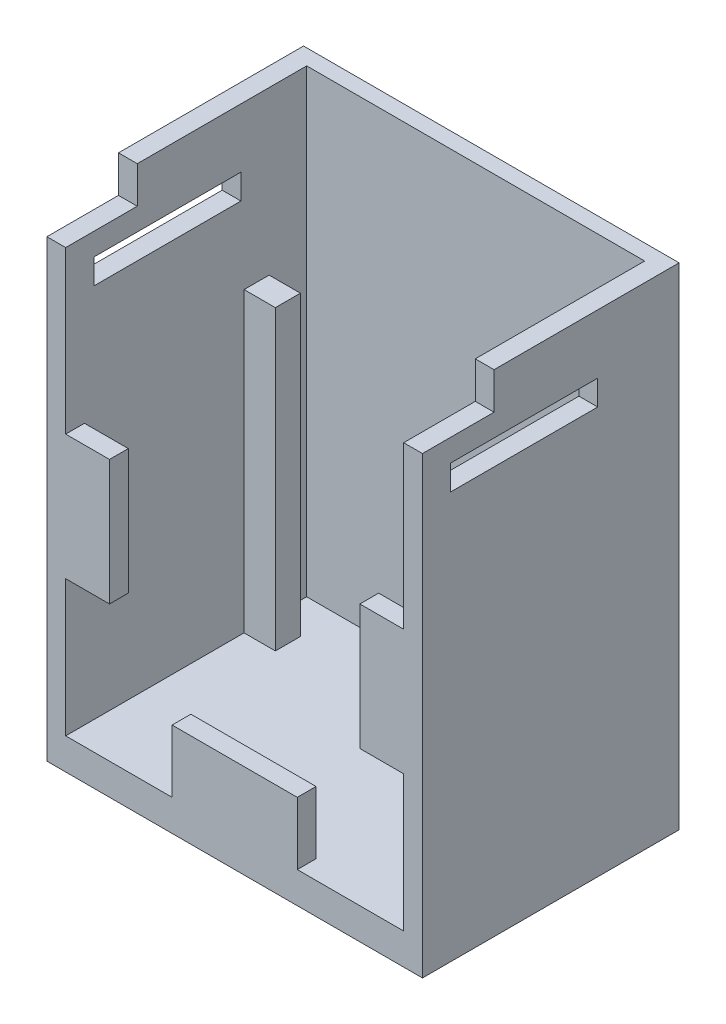
SolidWorks part; units mm, degrees
material "ABS"
ref_plane "Front Plane" through (0, 0, 0) normal (0, 0, 1) x (1, 0, 0)
ref_plane "Top Plane" through (0, 0, 0) normal (0, 1, 0) x (1, 0, 0)
ref_plane "Right Plane" through (0, 0, 0) normal (1, 0, 0) x (0, 0, -1)
sketch "Sketch1" plane through (0, 0, 0) normal (0, 0, 1) x (1, 0, 0)
  line L1 (15.24, -25.4) -> (-15.24, -25.4)
  line L2 (15.24, -25.4) -> (15.24, 15.24)
  line L3 (15.24, 15.24) -> (-15.24, 15.24)
  line L4 (-15.24, -25.4) -> (-15.24, 15.24)
  point P0 (0, 0)
  dimension "D1" = 30.48
  dimension "D2" = 40.64
extrude "Initial Block" add sketch "Sketch1" along normal blind 19.05 and the other way blind 1.778
sketch "Sketch2" plane through (0, 15.24, 0) normal (0, 1, 0) x (1, 0, 0)
  line L0 (15.24, 1.778) -> (-15.24, 1.778) construction
  line L1 (-13.716, 0.508) -> (13.716, 0.508)
  line L2 (-13.716, 0.508) -> (-13.716, -19.05)
  line L3 (-13.716, -19.05) -> (13.716, -19.05)
  line L4 (13.716, 0.508) -> (13.716, -19.05)
  line L5 (0, 1.778) -> (0, -14.7779) construction
  line L6 (15.24, -19.05) -> (-15.24, -19.05) construction
  point P9 (0, 1.778)
  point P11 (0, 0.508)
  point P12 (0, 0.508)
  dimension "D1" = 27.432
  dimension "D2" = 1.27
  dimension "D3" = 0
extrude "Initial Cut" cut sketch "Sketch2" against normal blind 38.1
ref_plane "Plane1" through (0, 0, 19.05) normal (0, 0, 1) x (1, 0, 0)
ref_plane "Plane2" through (0, 0, 0) normal (1, 0, 0) x (0, 0, -1)
sketch "Sketch20" plane through (0, 0, 19.05) normal (0, 0, 1) x (1, 0, 0)
  line L0 (-15.24, 9.398) -> (-15.24, -22.86) construction
  line L1 (-15.24, -22.86) -> (15.24, -22.86) construction
  line L2 (15.24, -22.86) -> (15.24, 9.398) construction
  line L3 (-15.24, -6.731) -> (15.24, -6.731) construction
  line L4 (15.24, 9.398) -> (-15.24, 9.398) construction
  line L5 (-15.24, -11.811) -> (-10.16, -11.811)
  line L6 (-15.24, -11.811) -> (-15.24, -1.651)
  line L7 (-15.24, -1.651) -> (-10.16, -1.651)
  line L8 (-10.16, -11.811) -> (-10.16, -1.651)
  line L9 (0, 9.398) -> (0, -22.86) construction
  line L10 (15.24, -11.811) -> (15.24, -1.651)
  line L11 (-5.08, -17.78) -> (5.08, -17.78)
  line L12 (-5.08, -17.78) -> (-5.08, -22.86)
  line L13 (-5.08, -22.86) -> (5.08, -22.86)
  line L14 (5.08, -17.78) -> (5.08, -22.86)
  line L15 (15.24, -11.811) -> (10.16, -11.811)
  line L16 (10.16, -11.811) -> (10.16, -1.651)
  line L17 (15.24, -1.651) -> (10.16, -1.651)
  line L19 (-13.716, -22.86) -> (13.716, -22.86) construction
  line L23 (-15.24, 15.24) -> (-15.24, -25.4) construction
  line L24 (15.24, -25.4) -> (15.24, 15.24) construction
  dimension "D1" = 10.16
  dimension "D2" = 5.08
  dimension "D3" = 10.16
  dimension "D4" = 5.08
  dimension "D5" = 5.08
  dimension "D6" = 10.16
extrude "Boss-Extrude1" add sketch "Sketch20" against normal blind 1.524
sketch "Sketch21" plane through (-13.716, 0, 0) normal (1, 0, 0) x (0, 0, -1)
  line L0 (-19.05, -1.651) -> (-19.05, 15.24) construction
  line L1 (-4.572, 1.27) -> (-2.54, 1.27)
  line L2 (-4.572, 1.27) -> (-4.572, -22.86)
  line L3 (-4.572, -22.86) -> (-2.54, -22.86)
  line L4 (-2.54, 1.27) -> (-2.54, -22.86)
  line L5 (0.508, 15.24) -> (-19.05, 15.24) construction
  line L6 (0.508, -22.86) -> (-19.05, -22.86) construction
  dimension "D1" = 2.032
  dimension "D2" = 14.478
  dimension "D3" = 13.97
  dimension "D4" = 0
extrude "Boss-Extrude2" add sketch "Sketch21" along normal blind 2.54 contours L4 L3 L2 L1
mirror "Mirror2" about plane through (0, 0, 0) normal (1, 0, 0) of "Boss-Extrude2"
sketch "Sketch27" plane through (15.24, 0, 0) normal (1, 0, 0) x (0, 0, -1)
  line L0 (-16.764, 9.652) -> (-4.826, 9.652)
  line L1 (-16.764, 9.652) -> (-16.764, 7.62)
  line L2 (-16.764, 7.62) -> (-4.826, 7.62)
  line L3 (-4.826, 9.652) -> (-4.826, 7.62)
  line L5 (-19.05, -25.4) -> (-19.05, 15.24) construction
  line L7 (1.778, -25.4) -> (-19.05, -25.4) construction
  dimension "D1" = 11.938
  dimension "D2" = 2.032
  dimension "D3" = 33.02
  dimension "D4" = 2.286
extrude "Cut-Extrude6" cut sketch "Sketch27" against normal up to next
mirror "Mirror6" about plane through (0, 0, 0) normal (1, 0, 0) of "Cut-Extrude6"
sketch "Sketch28" plane through (0, 0, 19.05) normal (0, 0, 1) x (1, 0, 0)
  line L0 (15.24, -25.4) -> (15.24, 15.24) construction
  line L1 (-15.24, 15.24) -> (15.24, 15.24)
  line L2 (-15.24, 15.24) -> (-15.24, 13.462)
  line L3 (-15.24, 13.462) -> (15.24, 13.462)
  line L4 (15.24, 15.24) -> (15.24, 13.462)
  dimension "D1" = 1.778
extrude "Cut-Extrude7" cut sketch "Sketch28" against normal through all
sketch "Sketch29" plane through (0, 0, 19.05) normal (0, 0, 1) x (1, 0, 0)
  line L0 (15.24, -25.4) -> (15.24, 13.462) construction
  line L1 (-15.24, 13.462) -> (15.24, 13.462)
  line L2 (-15.24, 13.462) -> (-15.24, 11.462)
  line L3 (-15.24, 11.462) -> (15.24, 11.462)
  line L4 (15.24, 13.462) -> (15.24, 11.462)
  dimension "D1" = 2
extrude "Cut-Extrude8" cut sketch "Sketch29" against normal blind 5.81
sketch "Sketch30" plane through (0, 13.462, 0) normal (0, 1, 0) x (1, 0, 0)
  line L0 (-15.24, -13.24) -> (-15.24, 1.778)
  line L1 (-15.24, 1.778) -> (15.24, 1.778)
  line L2 (15.24, 1.778) -> (15.24, -13.24)
  line L3 (15.24, -13.24) -> (13.716, -13.24)
  line L4 (13.716, -13.24) -> (13.716, 0.508)
  line L5 (13.716, 0.508) -> (-13.716, 0.508)
  line L6 (-13.716, 0.508) -> (-13.716, -13.24)
  line L7 (-13.716, -13.24) -> (-15.24, -13.24)
extrude "Boss-Extrude3" add sketch "Sketch30" along normal blind 0.99
